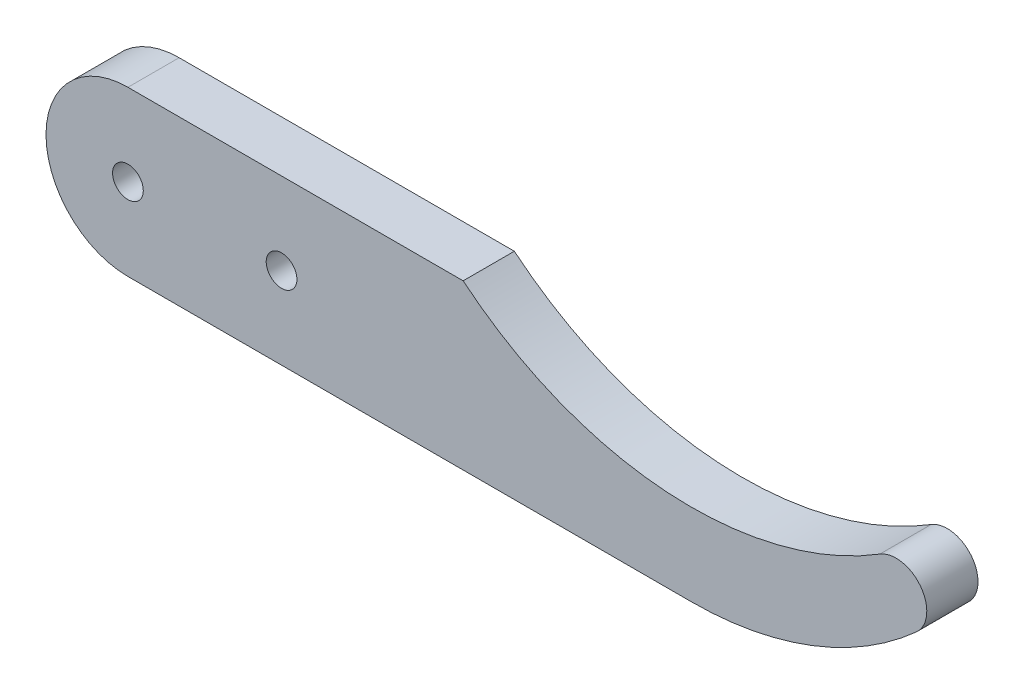
SolidWorks part; units mm, degrees
ref_plane "Plan de face" through (0, 0, 0) normal (0, 0, 1) x (1, 0, 0)
ref_plane "Plan de dessus" through (0, 0, 0) normal (0, 1, 0) x (1, 0, 0)
ref_plane "Plan de droite" through (0, 0, 0) normal (1, 0, 0) x (0, 0, -1)
sketch "Esquisse1" plane through (0, 0, 0) normal (0, 0, 1) x (1, 0, 0)
  line L0 (0, 0) -> (80, 0) construction
  line L2 (0, 0) -> (0, 35) construction
  line L3 (0, 35) -> (40, 35) construction
  line L4 (0, 8) -> (17.7289, 8)
  line L5 (58.4211, 5.2399) -> (60, 2.689) construction
  line L7 (0, -8) -> (40, -8)
  line L8 (40, 35) -> (40, -8) construction
  line L9 (0, 8) -> (-15, 8)
  line L10 (0, 0) -> (-15, 0) construction
  line L11 (0, -8) -> (-15, -8)
  circle A0 centre (0, 0) radius 1.5
  arc A1 (0, -8) -> (0, 8) centre (0, 0) cw construction
  circle A2 centre (40, 35) radius 35 construction
  arc A3 (17.7289, 8) -> (58.4211, 5.2399) centre (40, 35) ccw
  arc A4 (58.4211, 5.2399) -> (62.0097, 0.4616) centre (60, 2.689) cw
  arc A5 (40, -8) -> (62.0097, 0.4616) centre (40, 24.8557) ccw
  circle A6 centre (15, 0) radius 1.5 construction
  arc A7 (-15, 8) -> (-15, -8) centre (-15, 0) ccw
  circle A8 centre (-15, 0) radius 1.5
  dimension "D3" = 3
  dimension "D4" = 35
  dimension "D6" = 70
  dimension "D7" = 3
  dimension "D8" = 8
  dimension "D9" = 20
  dimension "D10" = 15
  dimension "D11" = 8
  dimension "D2" = 80
  dimension "D5" = 40
  dimension "D12" = 15
extrude "Boss.-Extru.1" add sketch "Esquisse1" along normal blind 5
